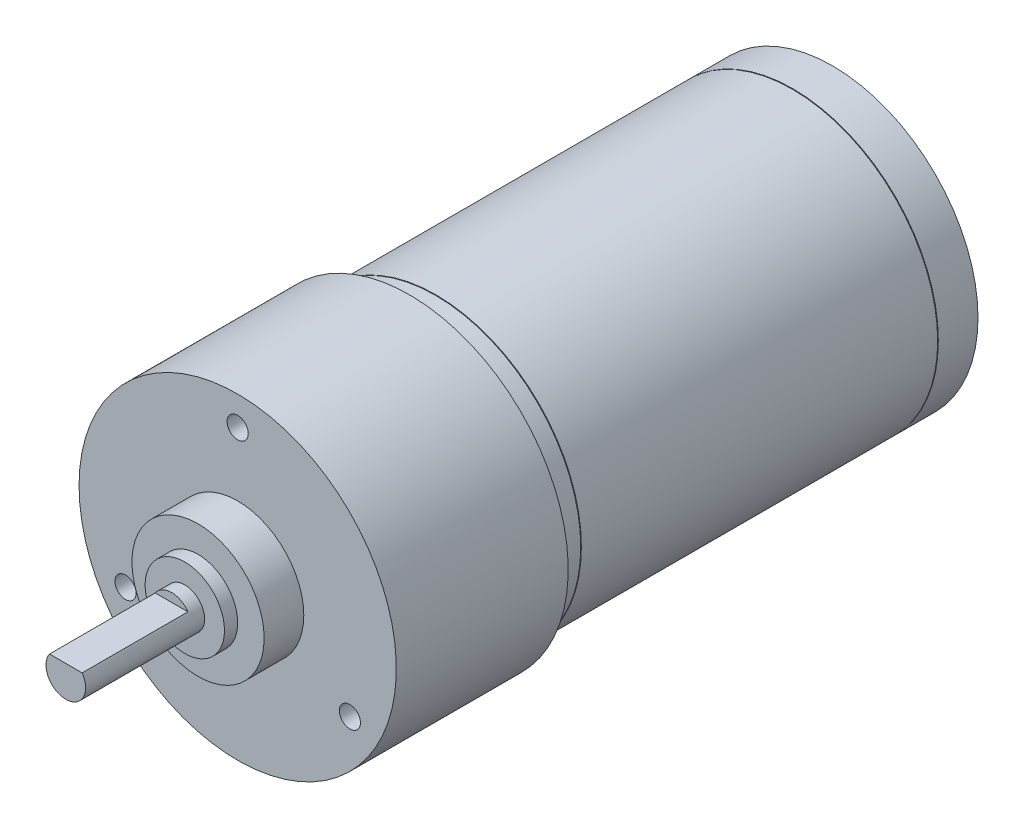
SolidWorks part; units mm, degrees
ref_plane "前视基准面" through (0, 0, 0) normal (0, 0, 1) x (1, 0, 0)
ref_plane "上视基准面" through (0, 0, 0) normal (0, 1, 0) x (1, 0, 0)
ref_plane "右视基准面" through (0, 0, 0) normal (1, 0, 0) x (0, 0, -1)
sketch "草图1" plane through (0, 0, 0) normal (0, 0, 1) x (1, 0, 0)
  circle A0 centre (0, 0) radius 11
  dimension "D1" = 22
extrude "凸台-拉伸1" add sketch "草图1" along normal blind 32
sketch "草图3" plane through (0, 0, 32) normal (0, 0, 1) x (1, 0, 0)
  line L0 (0, 8.5) -> (0, -8.5) construction
  circle A0 centre (0, 0) radius 8.5 construction
  dimension "D1" = 17
hole_wizard "M2 螺纹孔1" positions "3D草图1" profile "草图4" tap size "M2" standard "Gb"
sketch3d "3D草图1"
  point P0 (0, 8.5, 32)
  point P3 (0, -8.5, 32)
sketch "草图4" plane through (0, 8.5, 32) normal (1, 0, 0) x (0, -1, 0)
  line L0 (0, 0) -> (0, 5.6807)
  line L1 (0, 5.6807) -> (0.8, 5.2)
  line L2 (0.8, 5.2) -> (0.8, 0)
  line L5 (0.8, 0) -> (0, 0)
  line L10 (0, 5.6807) -> (-0.8, 5.2) construction
  line L11 (0, -6.35) -> (0, 107.95) construction
  dimension "螺纹孔钻头直径" = 1.6
  dimension "螺纹孔钻头深度" = 5.2
  dimension "导头角度" = 118
cosmetic thread "孔螺蚊线1" parameters "D1"=4, "D2"=2
cosmetic thread "孔螺蚊线2" parameters "D1"=4, "D2"=2
sketch "草图5" plane through (0, 0, 0) normal (0, 0, -1) x (-1, 0, 0)
  circle A0 centre (0, 0) radius 11.8384
  circle A1 centre (0, 0) radius 10.75
  dimension "D1" = 21.5
extrude "切除-拉伸1" cut sketch "草图5" against normal blind 0.05 from offset 3 offset against normal yes
extrude "切除-拉伸2" cut sketch "草图5<2>" against normal blind 0.05 from offset 30 offset against normal yes
sketch "草图5<2>" plane through (0, 0, 0) normal (0, 0, -1) x (-1, 0, 0) same geometry as "草图5"
sketch "草图6" plane through (0, 0, 32) normal (0, 0, 1) x (1, 0, 0)
  circle A0 centre (0, 0) radius 12
  dimension "D1" = 24
extrude "凸台-拉伸2" add sketch "草图6" along normal blind 13
sketch "草图7" plane through (0, 0, 45) normal (0, 0, 1) x (1, 0, 0)
  circle A0 centre (0, 0) radius 5
  dimension "D1" = 10
extrude "凸台-拉伸3" add sketch "草图7" along normal blind 3
sketch "草图8" plane through (0, 0, 45) normal (0, 0, 1) x (1, 0, 0)
  circle A0 centre (0, 0) radius 3
  dimension "D1" = 6
extrude "凸台-拉伸4" add sketch "草图8" along normal blind 4
sketch "草图9" plane through (0, 0, 45) normal (0, 0, 1) x (1, 0, 0)
  circle A0 centre (0, 0) radius 1.5
  dimension "D1" = 3
extrude "凸台-拉伸5" add sketch "草图9" along normal blind 13
sketch "草图10" plane through (0, 0, 58) normal (0, 0, 1) x (1, 0, 0)
  line L0 (-1.5, 0) -> (2.4759, 0) construction
  line L1 (-2.2371, 2.421) -> (2.9057, 2.421)
  line L2 (-2.2371, 2.421) -> (-2.2371, 0.85)
  line L3 (-2.2371, 0.85) -> (2.9057, 0.85)
  line L4 (2.9057, 2.421) -> (2.9057, 0.85)
  circle A0 centre (0, 0) radius 1.5 construction
  circle A1 centre (0, 0) radius 1.5 construction
  dimension "D1" = 0.85
extrude "切除-拉伸3" cut sketch "草图10" against normal blind 8
sketch "草图11" plane through (0, 0, 45) normal (0, 0, 1) x (1, 0, 0)
  circle A0 centre (0, 0) radius 9.8 construction
  point P3 (0, 9.8)
  point P6 (8.487, -4.9)
  point P7 (-8.487, -4.9)
  point P8 (0, 0)
  dimension "D1" = 19.6
  dimension "D2" = 3
hole_wizard "M2 螺纹孔2" positions "3D草图2" profile "草图12" tap size "M2" standard "Gb"
sketch3d "3D草图2"
  point P0 (0, 9.8, 45)
  point P3 (8.487, -4.9, 45)
  point P6 (-8.487, -4.9, 45)
sketch "草图12" plane through (0, 9.8, 45) normal (1, 0, 0) x (0, -1, 0)
  line L0 (0, 0) -> (0, 5.6807)
  line L1 (0, 5.6807) -> (0.8, 5.2)
  line L2 (0.8, 5.2) -> (0.8, 0)
  line L5 (0.8, 0) -> (0, 0)
  line L10 (0, 5.6807) -> (-0.8, 5.2) construction
  line L11 (0, -6.35) -> (0, 107.95) construction
  dimension "螺纹孔钻头直径" = 1.6
  dimension "螺纹孔钻头深度" = 5.2
  dimension "导头角度" = 118
cosmetic thread "孔螺蚊线3" parameters "D1"=4, "D2"=2
cosmetic thread "孔螺蚊线4" parameters "D1"=4, "D2"=2
cosmetic thread "孔螺蚊线5" parameters "D1"=4, "D2"=2
